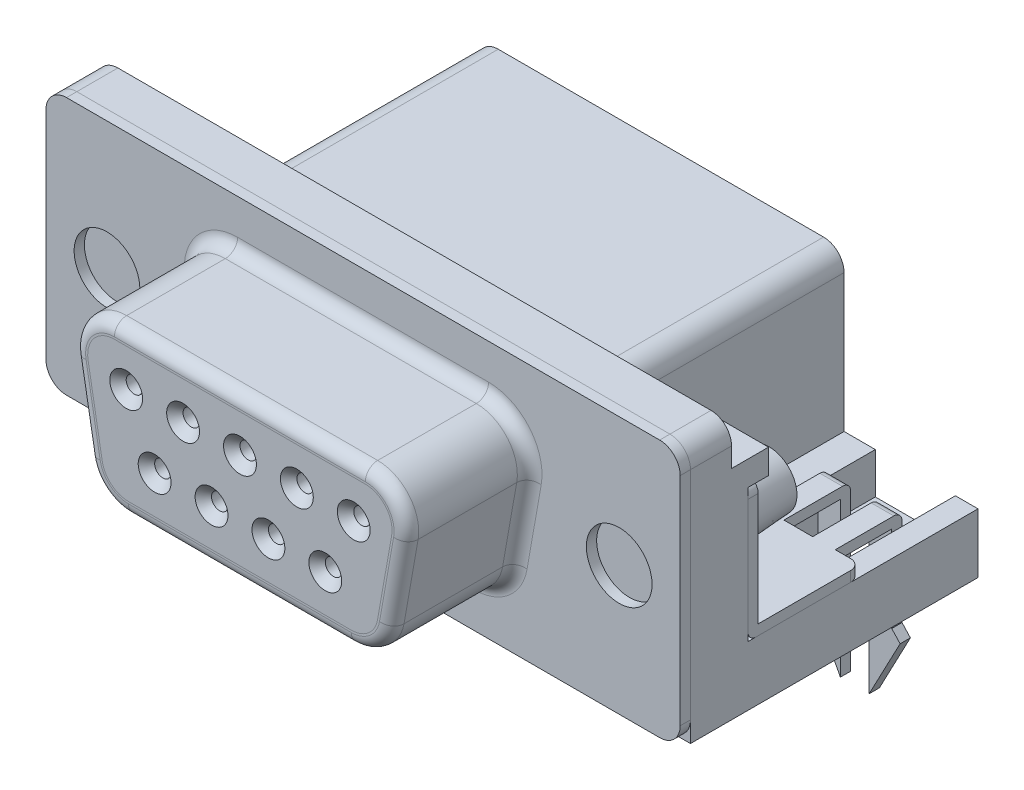
SolidWorks part; units mm, degrees
ref_plane "前视平面" through (0, 0, 0) normal (0, 0, 1) x (1, 0, 0)
ref_plane "上视平面" through (0, 0, 0) normal (0, 1, 0) x (1, 0, 0)
ref_plane "右视平面" through (0, 0, 0) normal (1, 0, 0) x (0, 0, -1)
sketch "底板" plane through (0, 0, 0) normal (0, 0, 1) x (1, 0, 0)
  line L1 (-14.44, 6.275) -> (14.44, 6.275)
  line L2 (-15.44, 5.275) -> (-15.44, -5.275)
  line L3 (-14.44, -6.275) -> (14.44, -6.275)
  line L4 (15.44, 5.275) -> (15.44, -5.275)
  arc A0 (14.44, 6.275) -> (15.44, 5.275) centre (14.44, 5.275) cw
  arc A1 (14.44, -6.275) -> (15.44, -5.275) centre (14.44, -5.275) ccw
  arc A2 (-14.44, 6.275) -> (-15.44, 5.275) centre (-14.44, 5.275) ccw
  arc A3 (-15.44, -5.275) -> (-14.44, -6.275) centre (-14.44, -5.275) ccw
  point P7 (15.44, 6.275)
  point P12 (-15.44, 6.275)
  dimension "D5" = 1
  dimension "D1" = 30.88
  dimension "D2" = 12.55
  dimension "D3" = 15.44
  dimension "D4" = 6.275
extrude "底板拉伸" add sketch "底板" along normal blind 0.5
sketch "接口外壳" plane through (0, 0, 0.5) normal (0, 0, 1) x (1, 0, 0)
  line L0 (8.0796, 1.6027) -> (7.3919, -2.2973)
  line L1 (-6.11, 3.95) -> (6.11, 3.95)
  line L2 (0, 0) -> (0, -16.7466) construction
  line L3 (-5.4223, -3.95) -> (5.4223, -3.95)
  line L4 (-8.0796, 1.6027) -> (-7.3919, -2.2973)
  line L5 (-15.44, 5.275) -> (-15.44, -5.275) construction
  line L6 (14.44, 6.275) -> (-14.44, 6.275) construction
  arc A0 (8.0796, 1.6027) -> (6.11, 3.95) centre (6.11, 1.95) ccw
  arc A1 (-5.4223, -3.95) -> (-7.3919, -2.2973) centre (-5.4223, -1.95) cw
  arc A2 (-8.0796, 1.6027) -> (-6.11, 3.95) centre (-6.11, 1.95) cw
  arc A3 (5.4223, -3.95) -> (7.3919, -2.2973) centre (5.4223, -1.95) ccw
  dimension "D5" = 4
  dimension "D1" = 10.8446
  dimension "D2" = 12.22
  dimension "D3" = 7.3604
  dimension "D4" = 2.325
extrude "接口外壳拉伸" add sketch "接口外壳" along normal blind 6
sketch "接口外壳内侧" plane through (0, 0, 6.5) normal (0, 0, 1) x (1, 0, 0)
  line L0 (-6.11, 3.25) -> (6.11, 3.25)
  line L1 (-7.3903, 1.7243) -> (-6.7026, -2.1757)
  line L2 (5.4223, -3.25) -> (-5.4223, -3.25)
  line L3 (6.7026, -2.1757) -> (7.3903, 1.7243)
  line L4 (6.11, 3.95) -> (-6.11, 3.95) construction
  arc A0 (-6.11, 3.25) -> (-7.3903, 1.7243) centre (-6.11, 1.95) ccw
  arc A1 (-6.7026, -2.1757) -> (-5.4223, -3.25) centre (-5.4223, -1.95) ccw
  arc A2 (5.4223, -3.25) -> (6.7026, -2.1757) centre (5.4223, -1.95) ccw
  arc A3 (7.3903, 1.7243) -> (6.11, 3.25) centre (6.11, 1.95) ccw
  dimension "D1" = 1.3
  dimension "D2" = 0.6894
  dimension "D3" = 1.377
  dimension "D4" = 1.9696
  dimension "D5" = 13.5019
  dimension "D6" = 0.7
extrude "接口外壳内侧拉伸切除" cut sketch "接口外壳内侧" against normal blind 6
fillet "接口外壳倒圆角" radius 0.6 16 edges at (7.6421, 3.2356, 0.5) (7.7358, -0.3473, 0.5) (6.7079, -3.4821, 0.5) (-6.7079, -3.4821, 0.5) (-7.7358, -0.3473, 0.5) (-7.6421, 3.2356, 0.5) (7.6421, 3.2356, 6.5) (7.7358, -0.3473, 6.5) (6.7079, -3.4821, 6.5) (-6.7079, -3.4821, 6.5) (-7.7358, -0.3473, 6.5) (-7.6421, 3.2356, 6.5) (0, -3.95, 0.5) (0, -3.95, 6.5) (0, 3.95, 0.5) (0, 3.95, 6.5)
sketch "绝缘体" plane through (0, 0, 0.5) normal (0, 0, 1) x (1, 0, 0)
  line L0 (-7.3903, 1.7243) -> (-6.7026, -2.1757)
  line L1 (6.11, 3.25) -> (-6.11, 3.25) construction
  line L4 (6.11, 3.25) -> (-6.11, 3.25)
  line L5 (-7.3903, 1.7243) -> (-6.7026, -2.1757)
  line L6 (6.11, 3.25) -> (-6.11, 3.25)
  line L7 (6.7026, -2.1757) -> (7.3903, 1.7243)
  line L8 (-5.4223, -3.25) -> (5.4223, -3.25)
  line L10 (-5.4223, -3.25) -> (5.4223, -3.25)
  line L11 (6.7026, -2.1757) -> (7.3903, 1.7243)
  arc A4 (7.3903, 1.7243) -> (6.11, 3.25) centre (6.11, 1.95) ccw
  arc A5 (-6.11, 3.25) -> (-7.3903, 1.7243) centre (-6.11, 1.95) ccw
  arc A6 (-6.7026, -2.1757) -> (-5.4223, -3.25) centre (-5.4223, -1.95) ccw
  arc A7 (5.4223, -3.25) -> (6.7026, -2.1757) centre (5.4223, -1.95) ccw
  arc A8 (7.3903, 1.7243) -> (6.11, 3.25) centre (6.11, 1.95) ccw
  arc A9 (-6.11, 3.25) -> (-7.3903, 1.7243) centre (-6.11, 1.95) ccw
  arc A10 (-6.7026, -2.1757) -> (-5.4223, -3.25) centre (-5.4223, -1.95) ccw
  arc A11 (5.4223, -3.25) -> (6.7026, -2.1757) centre (5.4223, -1.95) ccw
  circle A12 centre (5.545, 1.42) radius 0.4
  circle A13 centre (2.775, 1.42) radius 0.4
  circle A14 centre (0.005, 1.42) radius 0.4
  circle A15 centre (-2.765, 1.42) radius 0.4
  circle A16 centre (-5.535, 1.42) radius 0.4
  circle A25 centre (4.16, -1.42) radius 0.4
  circle A26 centre (1.39, -1.42) radius 0.4
  circle A27 centre (-1.38, -1.42) radius 0.4
  circle A28 centre (-4.15, -1.42) radius 0.4
  dimension "D2" = 0.8
  dimension "D3" = 1.8453
  dimension "D4" = 3.2303
  dimension "D5" = 4.6153
  dimension "D6" = 6.0003
  dimension "D7" = 7.3853
  dimension "D8" = 8.7703
  dimension "D9" = 10.1553
  dimension "D10" = 11.5403
  dimension "D11" = 12.9253
  dimension "D12" = 1.83
  dimension "D13" = 4.67
  dimension "D1" = 0
extrude "绝缘体拉伸" add sketch "绝缘体" along normal blind 6 separate body
chamfer "插针口倒角" distance 0.4 angle 45 9 edges at (5.945, 1.42, 6.5) (4.56, -1.42, 6.5) (3.175, 1.42, 6.5) (0.405, 1.42, 6.5) (1.79, -1.42, 6.5) (-0.98, -1.42, 6.5) (-2.365, 1.42, 6.5) (-5.135, 1.42, 6.5) (-3.75, -1.42, 6.5)
sketch "固定孔" plane through (0, 0, 0.5) normal (0, 0, 1) x (1, 0, 0)
  circle A0 centre (12.47, 0) radius 1.6
  circle A1 centre (-12.47, 0) radius 1.6
  dimension "D1" = 3.2
  dimension "D2" = 3.2
  dimension "D3" = 12.47
  dimension "D4" = 24.94
  dimension "D5" = 3.7995
extrude "固定孔切除" cut sketch "固定孔" against normal blind 6
sketch "后座基体" plane through (0, 0, 0) normal (0, 0, -1) x (-1, 0, 0)
  line L0 (-14.44, 6.275) -> (14.44, 6.275)
  line L1 (-15.44, -5.275) -> (-15.44, 5.275) construction
  line L2 (-15.44, 5.275) -> (-15.44, -6.275)
  line L3 (-15.44, -6.275) -> (15.44, -6.275)
  line L4 (15.44, 5.275) -> (15.44, -6.275)
  arc A0 (-14.44, 6.275) -> (-15.44, 5.275) centre (-14.44, 5.275) ccw
  arc A1 (14.44, 6.275) -> (15.44, 5.275) centre (14.44, 5.275) cw
  dimension "D1" = 1
  dimension "D2" = 30.88
  dimension "D3" = 12.55
extrude "后座基体拉伸" add sketch "后座基体" along normal blind 14 separate body
sketch "后座台阶" plane through (0, 0, -14) normal (0, 0, -1) x (-1, 0, 0)
  line L0 (-30.6506, -3.375) -> (-8.92, -3.375)
  line L1 (8.92, -3.375) -> (8.92, 4.325)
  line L2 (8.92, 4.325) -> (-8.92, 4.325)
  line L3 (-8.92, 4.325) -> (-8.92, -3.375)
  line L4 (8.92, -3.375) -> (30.0293, -3.375)
  line L5 (-30.6506, -3.375) -> (-30.6506, 10.8258)
  line L6 (30.0293, 10.8258) -> (-30.6506, 10.8258)
  line L7 (30.0293, 10.8258) -> (30.0293, -3.375)
  line L8 (15.44, -6.275) -> (15.44, 5.275) construction
  line L9 (14.44, 6.275) -> (-14.44, 6.275) construction
  dimension "D1" = 17.84
  dimension "D2" = 8.92
  dimension "D3" = 14.5893
  dimension "D4" = 46.0906
  dimension "D5" = 4.5508
  dimension "D6" = 1.95
  dimension "D7" = 9.65
extrude "后座台阶切除" cut sketch "后座台阶" against normal blind 12
fillet "后座台阶倒圆角" radius 1 2 edges at (-8.92, 4.325, -8) (8.92, 4.325, -8)
sketch "后座翼" plane through (15.44, 0, 0) normal (1, 0, 0) x (0, 0, -1)
  line L0 (2, 4.325) -> (2, -3.375)
  line L1 (2.8, -3.375) -> (2.8, 3.125)
  line L2 (2, -3.375) -> (2.8, -3.375)
  line L3 (2.8, 3.125) -> (3.8, 3.125)
  line L4 (2, -3.375) -> (14, -3.375) construction
  line L5 (3.8, 3.125) -> (3.8, 4.325)
  line L6 (2, 4.325) -> (14, 4.325) construction
  line L7 (3.8, 4.325) -> (2, 4.325)
  line L15 (14, -3.375) -> (2, -3.375) construction
  dimension "D1" = 1.8
  dimension "D2" = 0.8
  dimension "D3" = 1.2
extrude "后座翼拉伸" add sketch "后座翼" against normal up to surface (30.88 mm away) separate body up to face at (-15.44, -1.4583, -5.3333)
combine bodies "后座合并" operation type add bodies to combine 111 112
sketch "后座沟槽" plane through (0, -3.375, 0) normal (0, 1, 0) x (-1, 0, 0)
  line L1 (15.44, -2.8) -> (8.92, -2.8) construction
  line L2 (10.44, -2.8) -> (14.34, -2.8)
  line L3 (10.44, -2.8) -> (10.44, -18.8)
  line L4 (10.44, -18.8) -> (14.34, -18.8)
  line L6 (14.34, -2.8) -> (14.34, -18.8)
  line L7 (-15.44, -14) -> (15.44, -14) construction
  line L9 (0, -9.3047) -> (0, 7.3019) construction
  line L10 (-14.34, -2.8) -> (-14.34, -18.8)
  line L11 (-10.44, -18.8) -> (-14.34, -18.8)
  line L12 (-10.44, -2.8) -> (-10.44, -18.8)
  line L13 (-10.44, -2.8) -> (-14.34, -2.8)
  point P6 (0, -14)
  dimension "D1" = 3.9
  dimension "D2" = 10.44
  dimension "D3" = 16
extrude "后座沟槽切除" cut sketch "后座沟槽" against normal blind 2
sketch "后座沟槽2" plane through (0, -6.275, 0) normal (0, -1, 0) x (1, 0, 0)
  line L1 (-8.67, -2) -> (8.67, -2)
  line L2 (8.67, -15.6683) -> (8.67, -2)
  line L3 (-8.67, -15.6683) -> (8.67, -15.6683)
  line L4 (-8.67, -15.6683) -> (-8.67, -2)
  dimension "D1" = 17.34
  dimension "D2" = 2
  dimension "D3" = 8.67
  dimension "D4" = 15.6683
extrude "后座沟槽2切除" cut sketch "后座沟槽2" against normal blind 0.6
sketch "焊脚" plane through (0, -5.675, 0) normal (0, -1, 0) x (1, 0, 0)
  line L0 (8.67, -14) -> (8.67, -2) construction
  line L1 (8.67, -2) -> (-8.67, -2) construction
  line L25 (5.895, -12) -> (5.195, -12)
  line L26 (5.895, -12) -> (5.895, -12.7)
  line L27 (5.895, -12.7) -> (5.195, -12.7)
  line L28 (5.195, -12) -> (5.195, -12.7)
  line L29 (5.895, -12.35) -> (5.195, -12.35) construction
  line L30 (5.545, -12) -> (5.545, -12.7) construction
  line L31 (3.125, -12) -> (2.425, -12)
  line L32 (3.125, -12) -> (3.125, -12.7)
  line L33 (3.125, -12.7) -> (2.425, -12.7)
  line L34 (2.425, -12) -> (2.425, -12.7)
  line L35 (3.125, -12.35) -> (2.425, -12.35) construction
  line L36 (2.775, -12) -> (2.775, -12.7) construction
  line L37 (0.355, -12) -> (-0.345, -12)
  line L38 (0.355, -12) -> (0.355, -12.7)
  line L39 (0.355, -12.7) -> (-0.345, -12.7)
  line L40 (-0.345, -12) -> (-0.345, -12.7)
  line L41 (0.355, -12.35) -> (-0.345, -12.35) construction
  line L42 (0.005, -12) -> (0.005, -12.7) construction
  line L43 (-2.415, -12) -> (-3.115, -12)
  line L44 (-2.415, -12) -> (-2.415, -12.7)
  line L45 (-2.415, -12.7) -> (-3.115, -12.7)
  line L46 (-3.115, -12) -> (-3.115, -12.7)
  line L47 (-2.415, -12.35) -> (-3.115, -12.35) construction
  line L48 (-2.765, -12) -> (-2.765, -12.7) construction
  line L49 (-5.185, -12) -> (-5.885, -12)
  line L50 (-5.185, -12) -> (-5.185, -12.7)
  line L51 (-5.185, -12.7) -> (-5.885, -12.7)
  line L52 (-5.885, -12) -> (-5.885, -12.7)
  line L53 (-5.185, -12.35) -> (-5.885, -12.35) construction
  line L54 (-5.535, -12) -> (-5.535, -12.7) construction
  line L103 (4.51, -9.86) -> (3.81, -9.86)
  line L104 (4.51, -9.16) -> (4.51, -9.86)
  line L105 (4.51, -9.16) -> (3.81, -9.16)
  line L106 (3.81, -9.16) -> (3.81, -9.86)
  line L107 (4.16, -9.16) -> (4.16, -9.86) construction
  line L108 (4.51, -9.51) -> (3.81, -9.51) construction
  line L109 (1.74, -9.86) -> (1.04, -9.86)
  line L110 (1.74, -9.16) -> (1.74, -9.86)
  line L111 (1.74, -9.16) -> (1.04, -9.16)
  line L112 (1.04, -9.16) -> (1.04, -9.86)
  line L113 (1.39, -9.16) -> (1.39, -9.86) construction
  line L114 (1.74, -9.51) -> (1.04, -9.51) construction
  line L115 (-1.03, -9.86) -> (-1.73, -9.86)
  line L116 (-1.03, -9.16) -> (-1.03, -9.86)
  line L117 (-1.03, -9.16) -> (-1.73, -9.16)
  line L118 (-1.73, -9.16) -> (-1.73, -9.86)
  line L119 (-1.38, -9.16) -> (-1.38, -9.86) construction
  line L120 (-1.03, -9.51) -> (-1.73, -9.51) construction
  line L121 (-3.8, -9.86) -> (-4.5, -9.86)
  line L122 (-3.8, -9.16) -> (-3.8, -9.86)
  line L123 (-3.8, -9.16) -> (-4.5, -9.16)
  line L124 (-4.5, -9.16) -> (-4.5, -9.86)
  line L125 (-4.15, -9.16) -> (-4.15, -9.86) construction
  line L126 (-3.8, -9.51) -> (-4.5, -9.51) construction
  dimension "D2" = 10
  dimension "D4" = 2.775
  dimension "D5" = 3.125
  dimension "D6" = 4.16
  dimension "D7" = 5.545
  dimension "D8" = 6.93
  dimension "D9" = 8.315
  dimension "D10" = 9.7
  dimension "D11" = 11.085
  dimension "D12" = 12.47
  dimension "D13" = 13.855
  dimension "D30" = 7.16
extrude "焊脚拉伸" add sketch "焊脚" along normal blind 4.4 and the other way blind 2 separate body
sketch "焊脚沟" plane through (0, -5.675, 0) normal (0, -1, 0) x (1, 0, 0)
  line L0 (8.67, -14) -> (8.67, -2) construction
  line L1 (8.67, -2) -> (-8.67, -2) construction
  line L32 (5.895, -12) -> (5.895, -16.0355)
  line L33 (5.895, -12) -> (5.195, -12)
  line L34 (5.195, -12) -> (5.195, -16.0355)
  line L35 (5.195, -16.0355) -> (5.895, -16.0355)
  line L36 (4.51, -9.16) -> (3.81, -9.16)
  line L37 (4.51, -9.16) -> (4.51, -16.0355)
  line L38 (4.51, -16.0355) -> (3.81, -16.0355)
  line L39 (3.81, -9.16) -> (3.81, -16.0355)
  line L40 (3.125, -12) -> (3.125, -16.0355)
  line L41 (3.125, -12) -> (2.425, -12)
  line L42 (2.425, -12) -> (2.425, -16.0355)
  line L43 (2.425, -16.0355) -> (3.125, -16.0355)
  line L44 (1.74, -9.16) -> (1.04, -9.16)
  line L45 (1.74, -9.16) -> (1.74, -16.0355)
  line L46 (1.74, -16.0355) -> (1.04, -16.0355)
  line L47 (1.04, -9.16) -> (1.04, -16.0355)
  line L48 (0.355, -12) -> (0.355, -16.0355)
  line L49 (0.355, -12) -> (-0.345, -12)
  line L50 (-0.345, -12) -> (-0.345, -16.0355)
  line L51 (-0.345, -16.0355) -> (0.355, -16.0355)
  line L52 (-1.03, -9.16) -> (-1.73, -9.16)
  line L53 (-1.03, -9.16) -> (-1.03, -16.0355)
  line L54 (-1.03, -16.0355) -> (-1.73, -16.0355)
  line L55 (-1.73, -9.16) -> (-1.73, -16.0355)
  line L56 (-2.415, -12) -> (-2.415, -16.0355)
  line L57 (-2.415, -12) -> (-3.115, -12)
  line L58 (-3.115, -12) -> (-3.115, -16.0355)
  line L59 (-3.115, -16.0355) -> (-2.415, -16.0355)
  line L60 (-3.8, -9.16) -> (-4.5, -9.16)
  line L61 (-3.8, -9.16) -> (-3.8, -16.0355)
  line L62 (-3.8, -16.0355) -> (-4.5, -16.0355)
  line L63 (-4.5, -9.16) -> (-4.5, -16.0355)
  line L64 (-5.185, -12) -> (-5.185, -16.0355)
  line L65 (-5.185, -12) -> (-5.885, -12)
  line L66 (-5.885, -12) -> (-5.885, -16.0355)
  line L67 (-5.885, -16.0355) -> (-5.185, -16.0355)
  dimension "D2" = 7.16
  dimension "D3" = 14.0355
  dimension "D7" = 2.775
  dimension "D8" = 3.475
  dimension "D9" = 4.16
  dimension "D10" = 5.545
  dimension "D11" = 6.93
  dimension "D12" = 8.315
  dimension "D13" = 9.7
  dimension "D14" = 11.085
  dimension "D15" = 12.47
  dimension "D16" = 13.855
  dimension "D18" = 10
extrude "焊脚沟切除" cut sketch "焊脚沟" against normal blind 2
sketch "底座安装孔" plane through (0, -5.375, 0) normal (0, 1, 0) x (-1, 0, 0)
  line L1 (14.34, -2.8) -> (10.44, -2.8) construction
  line L2 (-10.44, -9.3) -> (-10.44, -11.3)
  line L3 (-14.34, -9.3) -> (-14.34, -11.3)
  line L4 (0, 0) -> (0, 17.0288) construction
  line L5 (-10.44, -14) -> (-10.44, -2.8) construction
  line L6 (-10.44, -2.8) -> (-14.34, -2.8) construction
  line L7 (14.34, -9.3) -> (14.34, -11.3)
  line L8 (10.44, -9.3) -> (10.44, -11.3)
  arc A0 (-14.34, -11.3) -> (-10.44, -11.3) centre (-12.39, -11.3) ccw
  arc A1 (10.44, -9.3) -> (14.34, -9.3) centre (12.39, -9.3) cw
  arc A2 (14.34, -11.3) -> (10.44, -11.3) centre (12.39, -11.3) cw
  arc A3 (-10.44, -9.3) -> (-14.34, -9.3) centre (-12.39, -9.3) ccw
  point P18 (63.8339, -26.9397)
  point P19 (31.4279, -17.5812)
  dimension "D1" = 1.95
  dimension "D2" = 6.5
  dimension "D3" = 8.5
extrude "底座安装孔切除" cut sketch "底座安装孔" against normal blind 4
sketch "卡脚垫" plane through (0, 0, -2.8) normal (0, 0, -1) x (-1, 0, 0)
  line L1 (-14.94, 3.125) -> (-9.9424, 3.125)
  line L2 (-15.44, 2.625) -> (-15.44, -3.375)
  line L3 (-15.44, -3.375) -> (-9.4424, -3.375)
  line L4 (-9.4424, 2.625) -> (-9.4424, -3.375)
  arc A0 (-14.94, 3.125) -> (-15.44, 2.625) centre (-14.94, 2.625) ccw
  arc A1 (-9.9424, 3.125) -> (-9.4424, 2.625) centre (-9.9424, 2.625) cw
  point P8 (-15.44, 3.125)
  dimension "D1" = 0.5
  dimension "D2" = 9.4424
  dimension "D3" = 15.44
  dimension "D4" = 3.125
  dimension "D5" = 3.375
extrude "卡脚垫拉伸" add sketch "卡脚垫" along normal blind 0.5 separate body
sketch "卡脚1" plane through (0, -3.375, 0) normal (0, 1, 0) x (-1, 0, 0)
  line L1 (-9.9424, -8.3) -> (-10.59, -8.3)
  line L2 (-9.4424, -3.3) -> (-9.4424, -7.8)
  line L3 (-9.4424, -3.3) -> (-15.44, -3.3)
  line L4 (-15.44, -3.3) -> (-15.44, -7.8)
  line L5 (-14.19, -8.3) -> (-14.19, -11.55)
  line L6 (-14.19, -11.55) -> (-13.09, -11.55)
  line L7 (-13.09, -11.55) -> (-13.09, -8.3)
  line L8 (-13.09, -8.3) -> (-11.69, -8.3)
  line L9 (-11.69, -8.3) -> (-11.69, -11.55)
  line L10 (-11.69, -11.55) -> (-10.59, -11.55)
  line L11 (-10.59, -11.55) -> (-10.59, -8.3)
  line L15 (-14.19, -8.3) -> (-14.94, -8.3)
  arc A0 (-14.94, -8.3) -> (-15.44, -7.8) centre (-14.94, -7.8) cw
  arc A1 (-9.4424, -7.8) -> (-9.9424, -8.3) centre (-9.9424, -7.8) cw
  point P9 (-15.44, -8.3)
  dimension "D2" = 10.59
  dimension "D1" = 0.5
  dimension "D3" = 11.69
  dimension "D4" = 13.09
  dimension "D5" = 8.3
  dimension "D6" = 15.44
  dimension "D7" = 11.55
extrude "卡脚1拉伸" add sketch "卡脚1" along normal blind 0.5 separate body contours A1 L2 L3 L15 L5 L6 L7 | A0 L15 L3 | L10 L11 L9 region at (12.4313, -3.375, -6.5895)
combine bodies "卡脚合并" operation type add bodies to combine 143 144
fillet "卡脚折弯外圆角" radius 0.4 1 edges at (12.4412, -3.375, -2.8)
sketch "卡脚2" plane through (0, 0, -11.55) normal (0, 0, -1) x (-1, 0, 0)
  line L0 (-14.19, -3.375) -> (-14.19, -7.5721)
  line L1 (-14.19, -7.5721) -> (-14.5975, -8.013)
  line L2 (-14.5975, -8.013) -> (-13.09, -10.875)
  line L3 (-13.09, -10.875) -> (-13.09, -3.375)
  line L4 (-14.19, -3.375) -> (-13.09, -3.375) construction
  line L5 (-13.09, -3.375) -> (-14.19, -3.375)
  line L6 (-14.19, -2.875) -> (-14.94, -2.875) construction
  line L7 (-12.39, -2.875) -> (-12.39, -7.5721) construction
  line L8 (-11.69, -2.875) -> (-13.09, -2.875) construction
  line L9 (-10.59, -7.5721) -> (-10.1825, -8.013)
  line L10 (-11.69, -10.875) -> (-11.69, -3.375)
  line L11 (-10.1825, -8.013) -> (-11.69, -10.875)
  line L12 (-10.59, -3.375) -> (-11.69, -3.375)
  line L13 (-10.59, -3.375) -> (-10.59, -7.5721)
  line L14 (-13.09, -2.875) -> (-13.09, -3.375) construction
  dimension "D1" = 8
  dimension "D2" = 2.9075
  dimension "D3" = 4.1971
  dimension "D4" = 4.638
extrude "卡脚2拉伸" add sketch "卡脚2" against normal blind 0.5 separate body
combine bodies "卡脚合并2" operation type add bodies to combine 146 147 145
fillet "卡脚折弯外圆角2" radius 0.4 2 edges at (11.14, -2.875, -11.55) (13.64, -2.875, -11.55)
sketch "卡脚圆柱" plane through (0, 0, -3.3) normal (0, 0, -1) x (-1, 0, 0)
  circle A0 centre (-12.47, 0) radius 1.6
  dimension "D1" = 3.2
extrude "卡脚圆柱拔模" add sketch "卡脚圆柱" along normal blind 3.5 draft 4 separate body
mirror "卡脚镜像" about plane through (0, 0, 0) normal (1, 0, 0) of bodies 149 148
sketch "底座凹面" plane through (0, 0, -14) normal (0, 0, -1) x (-1, 0, 0)
  line L0 (-7.32, 2.225) -> (7.32, 2.225)
  line L1 (-7.42, 2.325) -> (7.42, 2.325)
  line L2 (-7.42, 2.325) -> (-7.42, -3.675)
  line L3 (-7.42, -3.675) -> (7.42, -3.675)
  line L4 (7.42, 2.325) -> (7.42, -3.675)
  line L5 (7.32, 2.225) -> (7.32, -3.575)
  line L6 (-7.32, -3.575) -> (7.32, -3.575)
  line L7 (-7.32, 2.225) -> (-7.32, -3.575)
  line L9 (8.67, -6.275) -> (15.44, -6.275) construction
  dimension "D1" = 6
  dimension "D2" = 14.84
  dimension "D3" = 7.42
  dimension "D5" = 2.6
  dimension "D4" = 0.1
extrude "底座凹面切除" cut sketch "底座凹面" against normal blind 6.5
